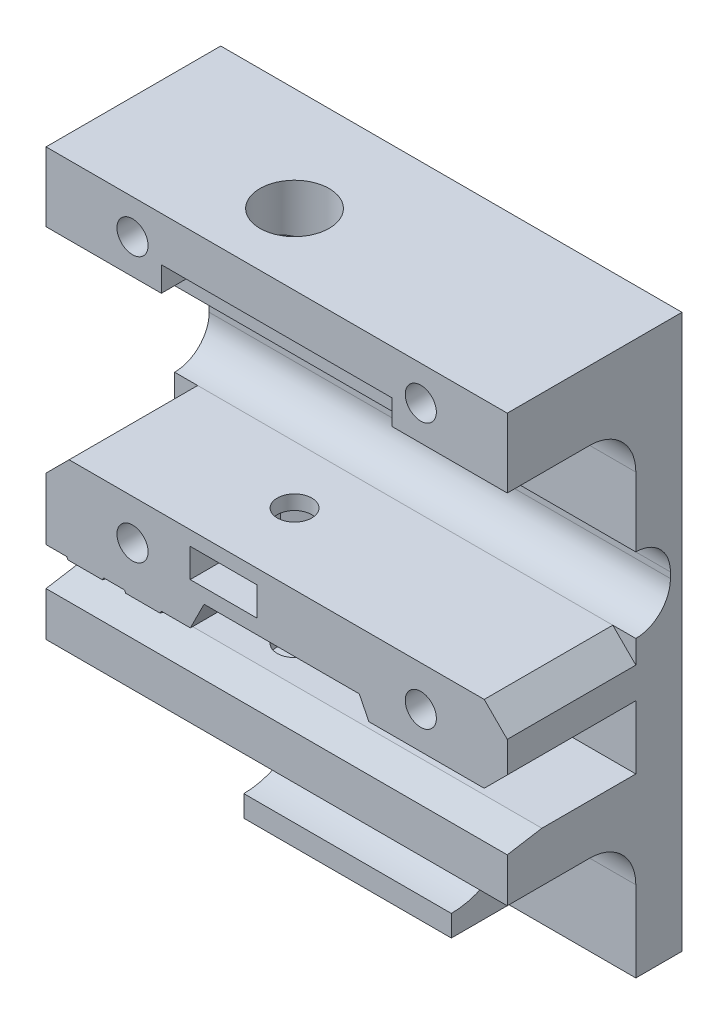
SolidWorks part; units mm, degrees
material "ABS"
ref_plane "Front Plane" through (0, 0, 0) normal (0, 0, 1) x (1, 0, 0)
ref_plane "Top Plane" through (0, 0, 0) normal (0, 1, 0) x (1, 0, 0)
ref_plane "Right Plane" through (0, 0, 0) normal (1, 0, 0) x (0, 0, -1)
sketch "Sketch1" plane through (0, 0, 0) normal (0, 0, 1) x (1, 0, 0)
  line L1 (-23.7591, 22) -> (52.715, 22) construction
  line L2 (0, -10) -> (0, 38)
  line L3 (0, 38) -> (40, 38)
  line L4 (40, -10) -> (40, 38)
  line L6 (0, -10) -> (40, -10)
  point P2 (0, 22)
  point P9 (40, 22)
  point P10 (0, 22)
  point P13 (40, 22)
  dimension "D1" = 48
  dimension "D2" = 40
extrude "Boss-Extrude1" add sketch "Sketch1" along normal blind 4
ref_plane "Plane2" through (0, 13, 0) normal (0, -1, 0) x (1, 0, 0)
sketch "Sketch2" plane through (0, 0, 4) normal (0, 0, 1) x (1, 0, 0)
  line L0 (20, 38) -> (20, 20.7808) construction
  line L1 (15.9, 33) -> (24.1, 33)
  line L2 (15.9, 33) -> (15.9, 23)
  line L3 (15.9, 23) -> (24.1, 23)
  line L4 (24.1, 33) -> (24.1, 23)
  line L5 (40, 38) -> (0, 38) construction
  line L6 (-2.2, 13) -> (2.2, 13) construction
  line L9 (2, 3) -> (10.2, 3)
  line L10 (2, 3) -> (2, -7)
  line L11 (2, -7) -> (10.2, -7)
  line L12 (10.2, 3) -> (10.2, -7)
  line L14 (29.8, 3) -> (29.8, -7)
  line L15 (38, -7) -> (29.8, -7)
  line L16 (38, 3) -> (38, -7)
  line L17 (38, 3) -> (29.8, 3)
  line L18 (15.9, 28) -> (24.1, 28) construction
  line L19 (2, -2) -> (38, -2) construction
  dimension "D1" = 8.2
  dimension "D2" = 10
  dimension "D3" = 20
  dimension "D4" = 4.1
  dimension "D5" = 30
  dimension "D6" = 2
extrude "Cut-Extrude1" [suppressed] cut sketch "Sketch2" against normal blind 1
sketch "Sketch3" [suppressed] plane through (0, 0, 3) normal (0, 0, 1) x (1, 0, 0)
  line L0 (15.9, 33) -> (15.9, 23) construction
  line L1 (15.9, 32.1) -> (24.1, 32.1)
  line L2 (15.9, 32.1) -> (15.9, 23.9)
  line L3 (15.9, 23.9) -> (24.1, 23.9)
  line L4 (24.1, 32.1) -> (24.1, 23.9)
  line L5 (24.1, 23) -> (24.1, 33) construction
  line L6 (24.1, 33) -> (15.9, 33) construction
  line L7 (15.9, 23) -> (24.1, 23) construction
  line L8 (2, 3) -> (2, -7) construction
  line L9 (2, 2.1) -> (10.2, 2.1)
  line L10 (2, 2.1) -> (2, -6.1)
  line L11 (2, -6.1) -> (10.2, -6.1)
  line L12 (10.2, 2.1) -> (10.2, -6.1)
  line L13 (10.2, -7) -> (10.2, 3) construction
  line L14 (29.8, 3) -> (29.8, -7) construction
  line L15 (29.8, 2.1) -> (38, 2.1)
  line L16 (29.8, 2.1) -> (29.8, -6.1)
  line L17 (29.8, -6.1) -> (38, -6.1)
  line L18 (38, 2.1) -> (38, -6.1)
  line L19 (38, -7) -> (38, 3) construction
  line L20 (2, -7) -> (10.2, -7) construction
  dimension "D1" = 0.9
  dimension "D2" = 0.9
  dimension "D3" = 0.9
extrude "Cut-Extrude2" [suppressed] cut sketch "Sketch3" against normal blind 4
chamfer "Chamfer1" [suppressed] distance 1 angle 45
sketch "Sketch4" [suppressed] plane through (0, 0, 3) normal (0, 0, 1) x (1, 0, 0)
  line L0 (24.1, 35.1) -> (15.9, 35.1) construction
  line L1 (15.9, 35.1) -> (15.9, 26.9) construction
  line L2 (2, 1) -> (38, 1) construction
  line L3 (2, 5.1) -> (2, -3.1) construction
  line L4 (38, -7) -> (38, 3) construction
  line L5 (6.1, 2.1) -> (6.1, -3.1) construction
  line L7 (2, -3.1) -> (10.2, -3.1) construction
  line L8 (33.9, 2.1) -> (33.9, -3.1) construction
  line L10 (29.8, -3.1) -> (38, -3.1) construction
  line L12 (10.2, 2.1) -> (2, 2.1) construction
  line L13 (38, 2.1) -> (29.8, 2.1) construction
  circle A0 centre (20, 31) radius 1.65
  circle A1 centre (6.1, 1) radius 1.65
  circle A2 centre (33.9, 1) radius 1.65
  dimension "D1" = 3.3
  dimension "D2" = 4.1
  dimension "D3" = 4.1
extrude "Cut-Extrude3" [suppressed] cut sketch "Sketch4" against normal through all
ref_plane "Plane1" through (20, 0, 0) normal (1, 0, 0) x (0, 0, -1)
sketch "Sketch5" plane through (0, 0, 4) normal (0, 0, 1) x (1, 0, 0)
  line L0 (-5.9966, 13) -> (42.103, 13) construction
  line L1 (1.8, 8.125) -> (0, 8.125)
  line L2 (40, 5.325) -> (40, 1)
  line L3 (0, 5.325) -> (40, 5.325)
  line L4 (40, 15.5) -> (40, 8.825)
  line L5 (40, 8.825) -> (28, 8.825)
  line L6 (20, -2.2) -> (20, 2.2) construction
  line L7 (0, -10) -> (40, -10) construction
  line L8 (0, 1) -> (40, 1)
  line L9 (27.1625, 10.5) -> (13.7035, 10.5)
  line L10 (28, 8.825) -> (27.1625, 10.5)
  line L12 (13.7035, 10.5) -> (12.516, 8.125)
  line L14 (-2.2, 13) -> (2.2, 13) construction
  line L23 (2.4, 6.925) -> (1.8, 8.125)
  line L27 (5, 8.125) -> (4.4, 6.925)
  line L28 (4.4, 6.925) -> (2.4, 6.925)
  line L29 (11, -10) -> (29, -10)
  line L30 (7.4, 6.925) -> (6.8, 8.125)
  line L31 (6.8, 8.125) -> (5, 8.125)
  line L32 (10, 8.125) -> (9.4, 6.925)
  line L33 (9.4, 6.925) -> (7.4, 6.925)
  line L34 (11, -10) -> (11, -5)
  line L36 (12.516, 8.125) -> (10, 8.125)
  line L40 (40, -10) -> (40, 38) construction
  line L42 (40, 15.5) -> (0, 15.5)
  line L43 (0, 15.5) -> (0, 8.125)
  line L46 (0, 38) -> (0, -10) construction
  line L47 (0, 32) -> (40, 32)
  line L48 (0, 32) -> (0, 38)
  line L49 (11, -5) -> (29, -5)
  line L50 (40, 32) -> (40, 38)
  line L51 (0, 38) -> (40, 38)
  line L52 (29, -10) -> (29, -5)
  line L53 (40, 38) -> (0, 38) construction
  line L62 (0, 5.325) -> (0, 1)
  point P84 (20, 5.325)
  dimension "D2" = 1.2
  dimension "D3" = 1.8
  dimension "D4" = 0.6
  dimension "D5" = 0.6
  dimension "D7" = 2
  dimension "D9" = 5
  dimension "D10" = 4.175
  dimension "D11" = 2.8
  dimension "D14" = 18
  dimension "D15" = 5
  dimension "D19" = 2.5
  dimension "D8" = 4.875
  dimension "D12" = 12
  dimension "D13" = 12
  dimension "D6" = 19
extrude "Boss-Extrude2" add sketch "Sketch5" along normal blind 11.15 and the other way up to surface (4 mm away) other way up to face at (20, 14, 0)
fillet "Fillet1" radius 4 2 edges at (20, 32, 4) (20, 1, 4) tangent propagation no
sketch "Sketch6" plane through (0, 0, 15.15) normal (0, 0, 1) x (1, 0, 0)
  line L0 (7.5, 41.1026) -> (7.5, 12.7734) construction
  line L2 (20, 38) -> (20, 13.7163) construction
  line L3 (20, -8.3325) -> (20, 8.3325) construction
  line L4 (-8.3325, 13) -> (8.3325, 13) construction
  line L6 (40, 38) -> (0, 38) construction
  circle A0 centre (7.5, 35) radius 1.35
  circle A1 centre (7.5, 12) radius 1.35
  circle A2 centre (32.5, 35) radius 1.35
  circle A3 centre (32.5, 12) radius 1.35
  dimension "D1" = 2.7
  dimension "D2" = 23
  dimension "D3" = 22
  dimension "D4" = 12.5
extrude "Cut-Extrude4" cut sketch "Sketch6" against normal through all
chamfer "Chamfer2" distance 2 angle 45 3 edges at (0, 15.5, 9.575) (40, 8.825, 9.575) (40, 15.5, 9.575)
sketch "Sketch7" plane through (0, 0, 4) normal (0, 0, 1) x (1, 0, 0)
  line L0 (0, 28) -> (0, 13.5) construction
  line L1 (0, 22) -> (40, 22)
  line L2 (0, 22) -> (0, 15.5)
  line L3 (0, 15.5) -> (40, 15.5)
  line L4 (40, 22) -> (40, 15.5)
  line L7 (38, 15.5) -> (2, 15.5) construction
  line L8 (-8.3325, 13) -> (8.3325, 13) construction
  dimension "D1" = 9
extrude "Cut-Extrude5" cut sketch "Sketch7" against normal blind 3
fillet "Fillet2" radius 3 2 edges at (20, 15.5, 1) (20, 22, 1)
chamfer "Chamfer3" distance 3 distance2 1 2 edges at (3.4, 6.925, 15.15) (8.4, 6.925, 15.15) first distance on face at (3.4, 6.925, 9.575) first distance on face at (8.4, 6.925, 9.575)
chamfer "Chamfer4" distance 3 distance2 0.5 1 edges at (20, 5.325, 15.15) first distance on face at (20, 5.325, 9.575)
sketch "Sketch8" plane through (20, 0, 0) normal (1, 0, 0) x (0, 0, -1)
  line L0 (-9, 28) -> (-9, -2) construction
  line L1 (-15.15, 38) -> (0, 38) construction
  line L2 (-4, 5.325) -> (-4, 10.825) construction
  line L4 (-9, 34.15) -> (-18.8563, 34.15)
  line L5 (-18.8563, 34.15) -> (-18.8563, 21.85)
  line L6 (-18.8563, 21.85) -> (-9, 21.85)
  line L8 (-18.8563, -10.4372) -> (-18.8563, -3.1589)
  line L9 (-18.8563, -3.1589) -> (-13.3487, 2.3487)
  line L10 (-9, -8.15) -> (-9, -10.4372)
  line L11 (-9, -10.4372) -> (-18.8563, -10.4372)
  arc A0 (-9, 21.85) -> (-9, 34.15) centre (-9, 28) ccw
  arc A1 (-9, -8.15) -> (-13.3487, 2.3487) centre (-9, -2) ccw
  dimension "D2" = 12.3
  dimension "D1" = 30
  dimension "D3" = 10
  dimension "D4" = 5
  dimension "D5" = 45
extrude "Cut-Extrude6" cut sketch "Sketch8" against normal blind 10 and the other way blind 10
sketch "Sketch12" plane through (0, 38, 0) normal (0, 1, 0) x (1, 0, 0)
  line L1 (10, -4) -> (0, -4) construction
  circle A0 centre (15.4, -9) radius 3
  dimension "D3" = 6
  dimension "D1" = 5
  dimension "D2" = 15.4
extrude "Cut-Extrude8" cut sketch "Sketch12" against normal up to surface (22.5 mm away) up to face at (20, 15.5, 9.575)
sketch "Sketch13" plane through (0, 15.5, 0) normal (0, 1, 0) x (1, 0, 0)
  circle A0 centre (15.4, -9) radius 1.5
  circle A1 centre (15.4, -9) radius 3 construction
  dimension "D1" = 3
extrude "Cut-Extrude10" cut sketch "Sketch13" against normal offset from surface (11.175 mm away) 1 up to face at (20, 5.325, 8.075) offset beyond the face yes
sketch "Sketch9" plane through (0, 13, 0) normal (0, -1, 0) x (1, 0, 0)
  line L0 (12.5, 16.8153) -> (18.3, 16.8153)
  line L1 (15.4, 5.6514) -> (18.3, 7.3257)
  line L2 (18.3, 7.3257) -> (18.3, 16.8153)
  line L5 (12.5, 16.8153) -> (12.5, 7.3257)
  line L6 (12.5, 7.3257) -> (15.4, 5.6514)
  line L8 (13.9872, 11.5329) -> (12.1308, 10.4612) [skipped]
  line L9 (16.8128, 11.5329) -> (14.9564, 12.6047) [skipped]
  circle A0 centre (15.4, 9) radius 2.9 construction
  arc A1 (18.4, 9) -> (12.4, 9) centre (15.4, 9) ccw construction
  dimension "D1" = 5.8
extrude "Cut-Extrude7" cut sketch "Sketch9" against normal blind 1.25 and the other way blind 1.25
